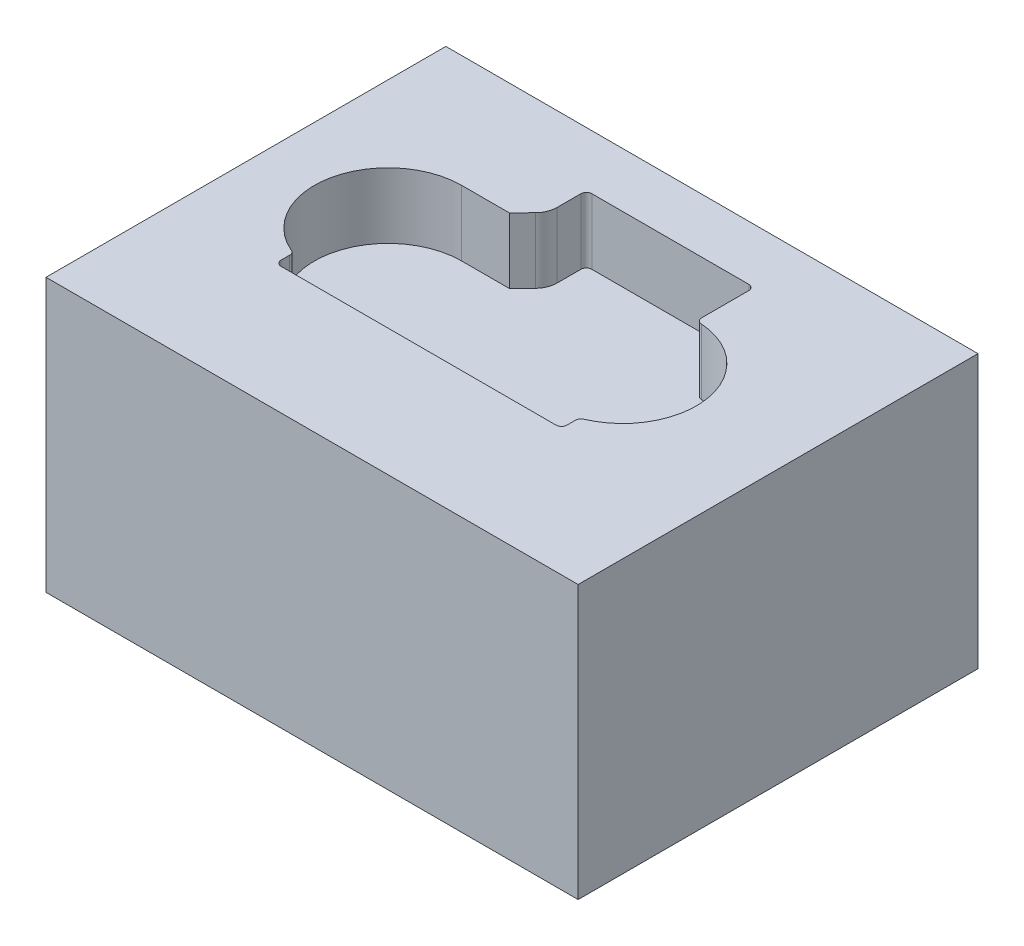
SolidWorks part; units mm, degrees
ref_plane "Front Plane" through (0, 0, 0) normal (0, 0, 1) x (1, 0, 0)
ref_plane "Top Plane" through (0, 0, 0) normal (0, 1, 0) x (1, 0, 0)
ref_plane "Right Plane" through (0, 0, 0) normal (1, 0, 0) x (0, 0, -1)
sketch "Sketch1" plane through (0, 0, 0) normal (0, 1, 0) x (1, 0, 0)
  line L1 (-145, 200) -> (145, 200)
  line L2 (-145, 200) -> (-145, -200)
  line L3 (-145, -200) -> (145, -200)
  line L4 (145, 200) -> (145, -200)
  line L5 (-145, 200) -> (145, -200) construction
  line L6 (-145, -200) -> (145, 200) construction
  point P0 (0, 0)
  dimension "D1" = 290
  dimension "D2" = 400
extrude "Boss-Extrude1" add sketch "Sketch1" along normal blind 35
sketch "Sketch2" plane through (0, 35, 0) normal (0, 1, 0) x (1, 0, 0)
  line L0 (145, -200) -> (145, 200) construction
  line L1 (-145, -200) -> (145, -200) construction
  line L2 (-145, 200) -> (-145, -200) construction
  line L3 (145, 200) -> (-145, 200) construction
  line L4 (145, -200) -> (145, 200)
  line L5 (-145, -200) -> (145, -200)
  line L6 (-145, 200) -> (-145, -200)
  line L7 (145, 200) -> (-145, 200)
  line L8 (135, -190) -> (135, 190)
  line L9 (135, 190) -> (-135, 190)
  line L10 (-135, 190) -> (-135, -190)
  line L11 (-135, -190) -> (135, -190)
  dimension "D1" = 10
extrude "Cut-Extrude2" cut sketch "Sketch2" against normal blind 10 contours L8 L9 L10 L11
sketch "Sketch3" plane through (0, 25, 0) normal (0, 1, 0) x (1, 0, 0)
  line L0 (0, 211.8692) -> (0, -222.8207) construction
  line L1 (-219.8723, 0) -> (201.339, 0) construction
  line L2 (135, 190) -> (-135, 190) construction
  line L3 (135, 190) -> (-135, 190) construction
  line L4 (135, 185) -> (-135, 185) construction
  line L5 (135, 165) -> (-135, 165) construction
  line L6 (-135, 190) -> (-135, -190) construction
  line L7 (-135, 190) -> (-135, -190) construction
  line L8 (-130, 190) -> (-130, -190) construction
  line L9 (-95, 190) -> (-95, -190) construction
  line L10 (-112.5, 190) -> (-112.5, -190) construction
  line L11 (-117.13, 185) -> (-101.75, 185)
  line L13 (-139, 190) -> (-139, -190)
  line L15 (-101.75, 199.739) -> (-101.75, 174.9169) construction
  line L16 (-99.4062, 166.62) -> (-99.4062, 165)
  line L17 (-101.75, 179.7) -> (-101.75, 185)
  line L18 (-125.5938, 165) -> (-99.4062, 165)
  line L19 (-125.5938, 166.62) -> (-125.5938, 165)
  line L20 (-123.25, 179.7) -> (-118.8793, 179.7)
  line L25 (-117.13, 185) -> (-117.13, 181.5)
  line L26 (-117.13, 181.5) -> (-118.8793, 179.7)
  line L61 (-117.13, 185) -> (-72.13, 185) construction
  arc A1 (-123.25, 179.7) -> (-125.5938, 166.62) centre (-123.25, 172.95) ccw
  arc A2 (-101.75, 179.7) -> (-99.4062, 166.62) centre (-101.75, 172.95) cw
  point P20 (135, 172.25)
  point P21 (-135, 173.09)
  point P24 (-126.7855, 190)
  point P25 (115.6811, -99.309)
  point P40 (-112.5, 165)
  dimension "D11" = 2.51
  dimension "D9" = 13.5
  dimension "D12" = 3.5
  dimension "D6" = 5.3
  dimension "D7" = 1.62
  dimension "D13" = 45
  dimension "D3" = 5
  dimension "D4" = 35
  dimension "D5" = 17.5
  dimension "D8" = 26.5
extrude "Cut-Extrude3" cut sketch "Sketch3" against normal blind 6 contours A2 L17 L11 L25 L26 L20 A1 L19 L18 L16 region at (-112.0602, 25, -173.939)
fillet "Fillet2" radius 2 1 edges at (-117.13, 22, -181.5)
fillet "Fillet4" radius 0.5 1 edges at (-125.5938, 22, -166.62)
fillet "Fillet5" radius 0.5 1 edges at (-99.4062, 22, -166.62)
fillet "Fillet6" radius 0.5 1 edges at (-101.75, 22, -179.7)
fillet "Fillet7" radius 0.5 1 edges at (-101.75, 22, -185)
fillet "Fillet8" radius 0.5 1 edges at (-117.13, 22, -185)
fillet "Fillet9" radius 0.5 2 edges at (-125.5938, 22, -165) (-99.4062, 22, -165)
sketch "Sketch4" plane through (0, 35, 0) normal (0, 1, 0) x (1, 0, 0)
  line L0 (-145, -200) -> (145, -200) construction
  line L1 (-135, 190) -> (-86.2505, 190)
  line L2 (-135, 190) -> (-135, 153.3673)
  line L3 (-135, 153.3673) -> (-86.2505, 153.3673)
  line L4 (-86.2505, 190) -> (-86.2505, 153.3673)
  line L5 (-145, 200) -> (145, 200)
  line L6 (-145, 200) -> (-145, -200)
  line L7 (-145, -200) -> (145, -200)
  line L8 (145, 200) -> (145, -200)
  line L9 (145, -200) -> (145, 200) construction
extrude "Cut-Extrude4" cut sketch "Sketch4" against normal through all
